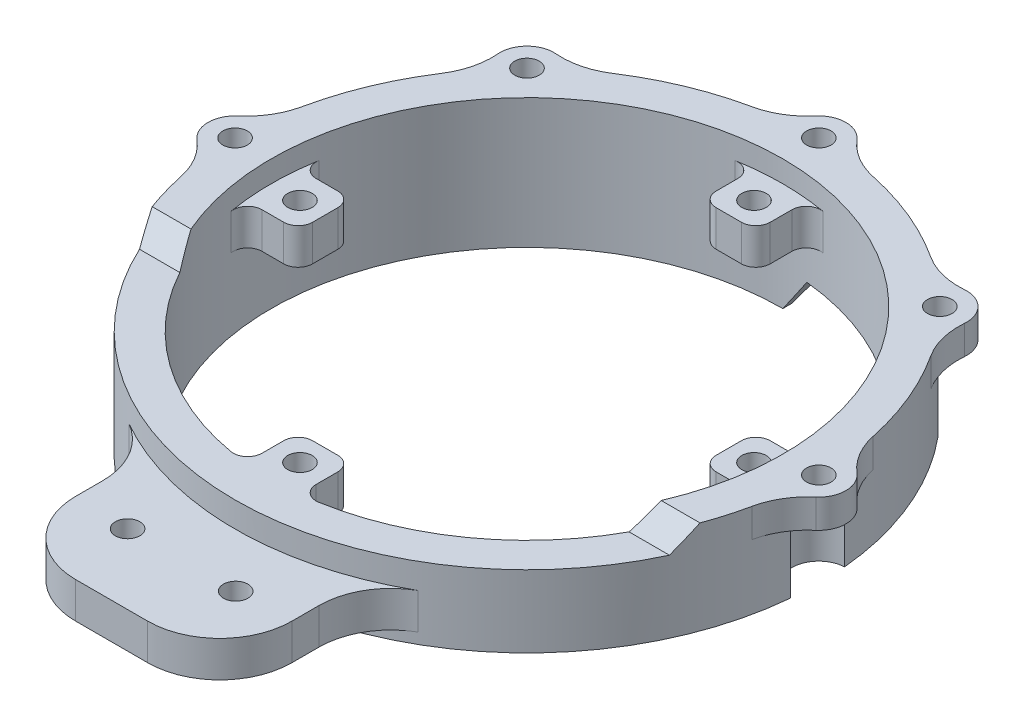
SolidWorks part; units mm, degrees
ref_plane "Alzado" through (0, 0, 0) normal (0, 0, 1) x (1, 0, 0)
ref_plane "Planta" through (0, 0, 0) normal (0, 1, 0) x (1, 0, 0)
ref_plane "Vista lateral" through (0, 0, 0) normal (1, 0, 0) x (0, 0, -1)
sketch "Croquis1" plane through (0, 0, 0) normal (0, 1, 0) x (1, 0, 0)
  circle A0 centre (0, 0) radius 35.5
  circle A1 centre (0, 0) radius 40.5
  dimension "D1" = 71
  dimension "D2" = 5
extrude "Saliente-Extruir1" add sketch "Croquis1" along normal mid plane 18
sketch "Croquis2" plane through (0, 0, 0) normal (0, -1, 0) x (1, 0, 0)
  line L0 (-15, 37.6198) -> (-15, 57.6198)
  line L1 (-15, 57.6198) -> (15, 57.6198)
  line L2 (15, 57.6198) -> (15, 37.6198)
  line L3 (0, 0) -> (0, 98.2113) construction
  circle A0 centre (0, 0) radius 40.5 construction
  arc A1 (15, 37.6198) -> (-15, 37.6198) centre (0, 0) ccw
  circle A2 centre (-7.5, 47.9166) radius 1.7
  circle A3 centre (7.5, 47.9166) radius 1.7
  circle A6 centre (0, 0) radius 48.5
  circle A7 centre (0, 0) radius 48.5 construction
  point P7 (0, 57.6198)
  dimension "D5" = 3.4
  dimension "D1" = 30
  dimension "D2" = 20
  dimension "D3" = 8
  dimension "D4" = 15
extrude "Saliente-Extruir2" add sketch "Croquis2" along normal mid plane 5
fillet "Redondeo1" radius 10 4 edges at (15, 0, 37.6198) (-15, 0, 37.6198) (-15, 0, 57.6198) (15, 0, 57.6198)
ref_plane "Plano1" through (0, 1, 0) normal (0, -1, 0) x (-1, 0, 0)
sketch "Croquis4" plane through (0, 1, 0) normal (0, -1, 0) x (-1, 0, 0)
  line L0 (0, -35.5) -> (0, 0) construction
  line L1 (-3.75, -35.3014) -> (-3.75, -28)
  line L2 (-3.75, -28) -> (3.75, -28)
  line L3 (3.75, -35.3014) -> (3.75, -28)
  circle A0 centre (0, 0) radius 35.5 construction
  arc A1 (-3.75, -35.3014) -> (3.75, -35.3014) centre (0, 0) ccw
  circle A2 centre (0, 0) radius 25 construction
  circle A3 centre (0, -31.5) radius 1.7
  circle A4 centre (0, 0) radius 31.5 construction
  point P12 (0, -28)
  dimension "D1" = 3.4
  dimension "D5" = 50
  dimension "D6" = 6.5
  dimension "D3" = 7.5
  dimension "D4" = 3.75
extrude "Saliente-Extruir3" add sketch "Croquis4" against normal blind 5
fillet "Redondeo2" radius 2 4 edges at (-3.75, 3.5, 35.3014) (3.75, 3.5, 28) (-3.75, 3.5, 28) (3.75, 3.5, 35.3014)
pattern_circular "MatrizC1" count 4 every 90 about axis through (0, 9, 0) along (0, 1, 0) of "Saliente-Extruir3", "Redondeo2"
hole_wizard "Refrentado para tornillo con cabeza plana de M31" positions "Croquis6" profile "Croquis7" counterbore size "M3" standard "ISO" end condition through all
sketch "Croquis6" plane through (0, -9, 0) normal (0, -1, 0) x (-1, 0, 0)
  circle A0 centre (0, 0) radius 40.5 construction
  point P0 (0, 40.5)
sketch "Croquis7" plane through (0, -9, -40.5) normal (1, 0, 0) x (0, 0, -1)
  line L0 (0, 0) -> (0, 18)
  line L1 (0, 18) -> (1.7, 18)
  line L3 (1.7, 18) -> (1.7, 14)
  line L4 (1.7, 14) -> (3.75, 14)
  line L5 (3.75, 14) -> (3.75, 0)
  line L7 (3.75, 0) -> (0, 0)
  line L11 (0, -6.35) -> (0, 107.95) construction
  dimension "Diámetro de taladro hasta el siguiente" = 3.4
  dimension "Profundidad de taladro hasta el siguiente" = 18
  dimension "Diámetro de refrentado" = 7.5
  dimension "Profundidad de refrentado" = 14
sketch "Croquis8" plane through (0, 9, 0) normal (0, 1, 0) x (1, 0, 0)
  circle A0 centre (0, 40.5) radius 3.75
  circle A1 centre (0, 40.5) radius 1.7
  arc A2 (-3.746, 40.3264) -> (3.746, 40.3264) centre (0, 40.5) ccw construction
  arc A3 (-3.746, 40.3264) -> (3.746, 40.3264) centre (0, 40.5) ccw construction
extrude "Saliente-Extruir4" add sketch "Croquis8" against normal up to surface (4 mm away) up to face at (0, 5, -39.0917)
pattern_circular "MatrizC2" count 3 every 45 about axis through (0, 9, 0) along (0, 1, 0) of "Saliente-Extruir4", "Refrentado para tornillo con cabeza plana de M31"
mirror "Simetría1" about plane through (0, 0, 0) normal (1, 0, 0) of "MatrizC2"
sketch "Croquis9" plane through (0, 9, 0) normal (0, 1, 0) x (1, 0, 0)
  line L0 (-36.7594, -17) -> (36.7594, -17)
  arc A0 (-40.3264, -3.746) -> (40.3264, -3.746) centre (0, 0) ccw construction
  arc A1 (-36.7594, -17) -> (36.7594, -17) centre (0, 0) ccw
  dimension "D1" = 17
extrude "Cortar-Extruir1" cut sketch "Croquis9" against normal up to surface (3 mm away) up to face at (0, 6, 29.8)
chamfer "Chaflán1" distance 3 angle 45 2 edges at (-33.9621, 9, 17) (33.9621, 9, 17)
fillet "Redondeo3" radius 10 10 edges at (-40.3264, 7, -3.746) (-40.3264, 7, 3.746) (-31.1639, 7, -25.8663) (-25.8663, 7, -31.1639) (-3.746, 7, -40.3264) (3.746, 7, -40.3264) (31.1639, 7, -25.8663) (25.8663, 7, -31.1639) (40.3264, 7, -3.746) (40.3264, 7, 3.746)
sketch "Croquis10" plane through (0, -9, 0) normal (0, -1, 0) x (1, 0, 0)
  line L0 (0, 40.5) -> (0, 35.5)
  line L1 (0, -35.5) -> (0, -40.5)
  arc A0 (0, -40.5) -> (0, 40.5) centre (0, 0) ccw
  arc A1 (0, -35.5) -> (0, 35.5) centre (0, 0) ccw
extrude "Cortar-Extruir2" cut sketch "Croquis10" against normal blind 5
chamfer "Chaflán2" distance 5 angle 35 2 edges at (0, -4, -36.125) (0, -4, 38) first distance on face at (0, -6.5, -36.125) first distance on face at (0, -6.5, 38)
